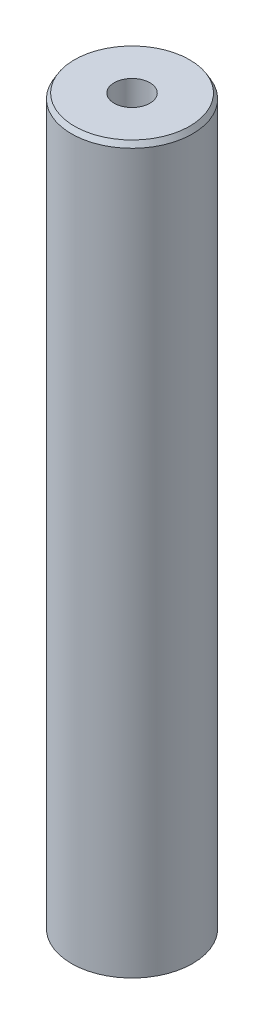
SolidWorks part; units mm, degrees
ref_plane "Front Plane" through (0, 0, 0) normal (0, 0, 1) x (1, 0, 0)
ref_plane "Top Plane" through (0, 0, 0) normal (0, 1, 0) x (1, 0, 0)
ref_plane "Right Plane" through (0, 0, 0) normal (1, 0, 0) x (0, 0, -1)
sketch "Sketch1" plane through (0, 0, 0) normal (0, 1, 0) x (1, 0, 0)
  circle A0 centre (0, 0) radius 50
  dimension "SHAFT_OD" = 100
extrude "Boss-Extrude1" add sketch "Sketch1" along normal blind 600
sketch "Sketch2" plane through (0, 0, 0) normal (0, 1, 0) x (1, 0, 0)
  circle A0 centre (0, 0) radius 14.7293
  dimension "BORE_D" = 29.4587
extrude "Cut-Extrude1" cut sketch "Sketch2" along normal through all
chamfer "Chamfer1" distance 4.2181 angle 30 2 edges at (0, 600, 50) (0, 0, 50) first distance on face at (0, 600, 50) first distance on face at (0, 0, 14.7293)
